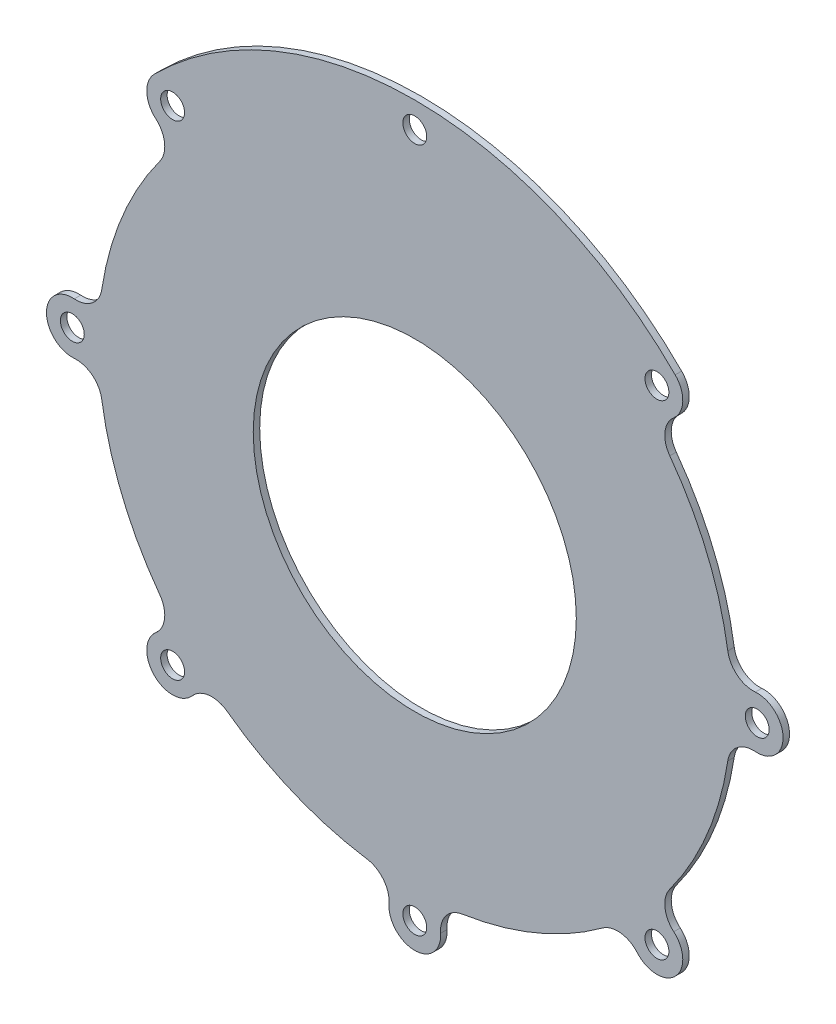
SolidWorks part; units mm, degrees
ref_plane "Ön Düzlem" through (0, 0, 0) normal (0, 0, 1) x (1, 0, 0)
ref_plane "Üst Düzlem" through (0, 0, 0) normal (0, 1, 0) x (1, 0, 0)
ref_plane "Sağ Düzlem" through (0, 0, 0) normal (1, 0, 0) x (0, 0, -1)
sketch "Sketch1" plane through (0, 0, 0) normal (0, 0, 1) x (1, 0, 0)
  circle A0 centre (0, 0) radius 25
  arc A1 (-39.4685, 29.0385) -> (-48.4418, 7.3751) centre (0, 0) ccw
  arc A2 (40.3051, 40.3051) -> (-40.3051, 40.3051) centre (0, 0) ccw
  circle A3 centre (0, -53) radius 1.85
  circle A4 centre (0, 0) radius 53 construction
  arc A5 (-3.9886, -52.6981) -> (3.9886, -52.6981) centre (0, -53) ccw
  arc A6 (7.3751, -48.4418) -> (4.0028, -52.8486) centre (7.9772, -52.3962) ccw
  arc A7 (-4.0028, -52.8486) -> (-7.3751, -48.4418) centre (-7.9772, -52.3962) ccw
  arc A8 (-29.0385, -39.4685) -> (-34.5392, -40.2001) centre (-31.409, -42.6904) ccw
  circle A9 centre (-37.4767, -37.4767) radius 1.85
  arc A10 (-40.0836, -34.4428) -> (-34.4428, -40.0836) centre (-37.4767, -37.4767) ccw
  arc A11 (-40.2001, -34.5392) -> (-39.4685, -29.0385) centre (-42.6904, -31.409) ccw
  arc A12 (-48.4418, -7.3751) -> (-52.8486, -4.0028) centre (-52.3962, -7.9772) ccw
  circle A13 centre (-53, 0) radius 1.85
  arc A14 (-52.6981, 3.9886) -> (-52.6981, -3.9886) centre (-53, 0) ccw
  arc A15 (-52.8486, 4.0028) -> (-48.4418, 7.3751) centre (-52.3962, 7.9772) ccw
  arc A16 (-39.4685, 29.0385) -> (-40.2001, 34.5392) centre (-42.6904, 31.409) ccw
  circle A17 centre (-37.4767, 37.4767) radius 1.85
  arc A18 (-40.3051, 40.3051) -> (-40.0836, 34.4428) centre (-37.4767, 37.4767) ccw
  circle A21 centre (0, 53) radius 1.85
  circle A25 centre (37.4767, 37.4767) radius 1.85
  arc A26 (40.0836, 34.4428) -> (40.3051, 40.3051) centre (37.4767, 37.4767) ccw
  arc A27 (40.2001, 34.5392) -> (39.4685, 29.0385) centre (42.6904, 31.409) ccw
  arc A28 (48.4418, 7.3751) -> (52.8486, 4.0028) centre (52.3962, 7.9772) ccw
  circle A29 centre (53, 0) radius 1.85
  arc A30 (52.6981, -3.9886) -> (52.6981, 3.9886) centre (53, 0) ccw
  arc A31 (52.8486, -4.0028) -> (48.4418, -7.3751) centre (52.3962, -7.9772) ccw
  arc A32 (39.4685, -29.0385) -> (40.2001, -34.5392) centre (42.6904, -31.409) ccw
  circle A33 centre (37.4767, -37.4767) radius 1.85
  arc A34 (34.4428, -40.0836) -> (40.0836, -34.4428) centre (37.4767, -37.4767) ccw
  arc A35 (34.5392, -40.2001) -> (29.0385, -39.4685) centre (31.409, -42.6904) ccw
  arc A36 (7.3751, -48.4418) -> (29.0385, -39.4685) centre (0, 0) ccw
  arc A37 (39.4685, -29.0385) -> (48.4418, -7.3751) centre (0, 0) ccw
  arc A38 (33.7795, 45.9124) -> (28.0999, 44.9377) centre (31.409, 42.6904) ccw [skipped]
  circle A39 centre (0, 53) radius 4 [skipped]
  circle A40 centre (7.9772, 52.3962) radius 4 [skipped]
  circle A41 centre (-7.9772, 52.3962) radius 4 [skipped]
  circle A42 centre (-31.409, 42.6904) radius 4 [skipped]
  arc A43 (-29.0385, -39.4685) -> (-7.3751, -48.4418) centre (0, 0) ccw
  arc A44 (48.4418, 7.3751) -> (39.4685, 29.0385) centre (0, 0) ccw
  arc A45 (-48.4418, -7.3751) -> (-39.4685, -29.0385) centre (0, 0) ccw
  point P22 (0, 0)
  point P23 (0, 0)
  point P24 (0, 0)
  point P61 (-48.4418, -7.9772)
  point P72 (0, 0)
  point P73 (0, 0)
  point P74 (0, 0)
  dimension "D1" = 50
  dimension "D2" = 98
  dimension "D3" = 114
  dimension "D4" = 3.7
  dimension "D5" = 106
  dimension "D6" = 8
  dimension "D7" = 8
extrude "Boss-Extrude1" add sketch "Sketch1" along normal blind 1 contours A12 A45 A11 A10 A8 A43 A7 A5 A6 A36 A35 A34 A32 A37 A31 A30 A28 A44 A27 A26 A2 A18 A16 A1 A15 A14 A0 A3 A9 A13 A17 A21 A25 A29 A33 region at (-31.409, 42.6904, 0) region at (-37.1188, 32.0431, 0) region at (-4.2309, 55.8991, 0) region at (-7.9772, 52.3962, 0) region at (4.2309, 55.8991, 0) region at (2.7484, 55.7484, 0) region at (7.9772, 52.3962, 0)
